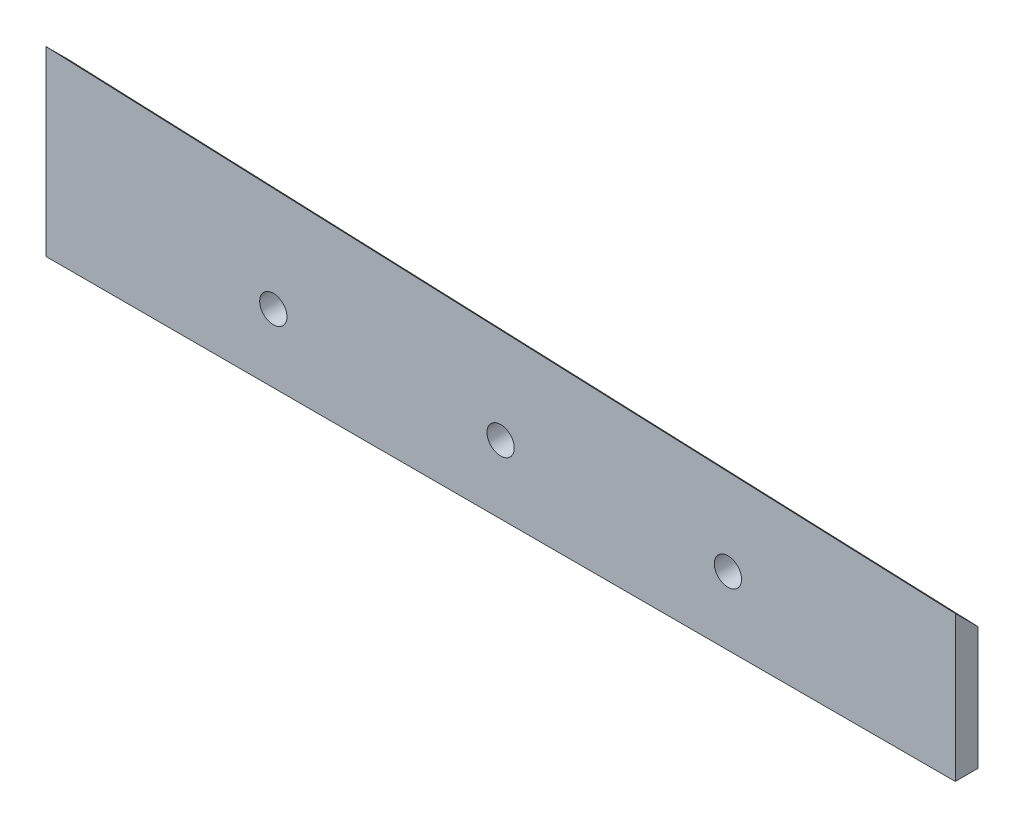
SolidWorks part; units mm, degrees
ref_plane "Front Plane" through (0, 0, 0) normal (0, 0, 1) x (1, 0, 0)
ref_plane "Top Plane" through (0, 0, 0) normal (0, 1, 0) x (1, 0, 0)
ref_plane "Right Plane" through (0, 0, 0) normal (1, 0, 0) x (0, 0, -1)
sketch "Sketch1" plane through (0, 0, 0) normal (1, 0, 0) x (0, 0, -1)
  line L1 (415.8269, -149.2325) -> (420.8269, -149.2325)
  line L2 (415.8269, -149.2325) -> (415.8269, -189.2325)
  line L3 (415.8269, -189.2325) -> (420.8269, -189.2325)
  line L4 (420.8269, -149.2325) -> (420.8269, -189.2325)
  dimension "D1" = 5
  dimension "D2" = 40
extrude "Boss-Extrude1" add sketch "Sketch1" along normal blind 200
sketch "Sketch3" plane through (0, 0, -415.8269) normal (0, 0, 1) x (1, 0, 0)
  line L0 (0, -149.2325) -> (200, -149.2325)
  line L1 (200, -149.2325) -> (200, -157.2325)
  line L2 (200, -149.2325) -> (200, -189.2325) construction
  line L3 (200, -157.2325) -> (0, -149.2325)
  dimension "D1" = 8
extrude "Cut-Extrude2" cut sketch "Sketch3" against normal up to surface (5 mm away) up to face at (100, -169.2325, -420.8269)
chamfer "Chamfer1" distance 5 angle 45 1 edges at (100, -153.2325, -420.8269)
sketch "Sketch2" plane through (0, 0, -420.8269) normal (0, 0, -1) x (-1, 0, 0)
  line L0 (0, -189.2325) -> (0, -154.2365) construction
  line L1 (-200, -189.2325) -> (0, -189.2325) construction
  circle A0 centre (-50, -174.2325) radius 3
  dimension "D1" = 6
  dimension "D2" = 50
  dimension "D3" = 15
extrude "Cut-Extrude1" cut sketch "Sketch2" against normal up to surface (5 mm away) up to face at (100, -171.2325, -415.8269)
pattern_linear "LPattern1" count 3 spacing 50 along (1, 0, 0) of "Cut-Extrude1"
